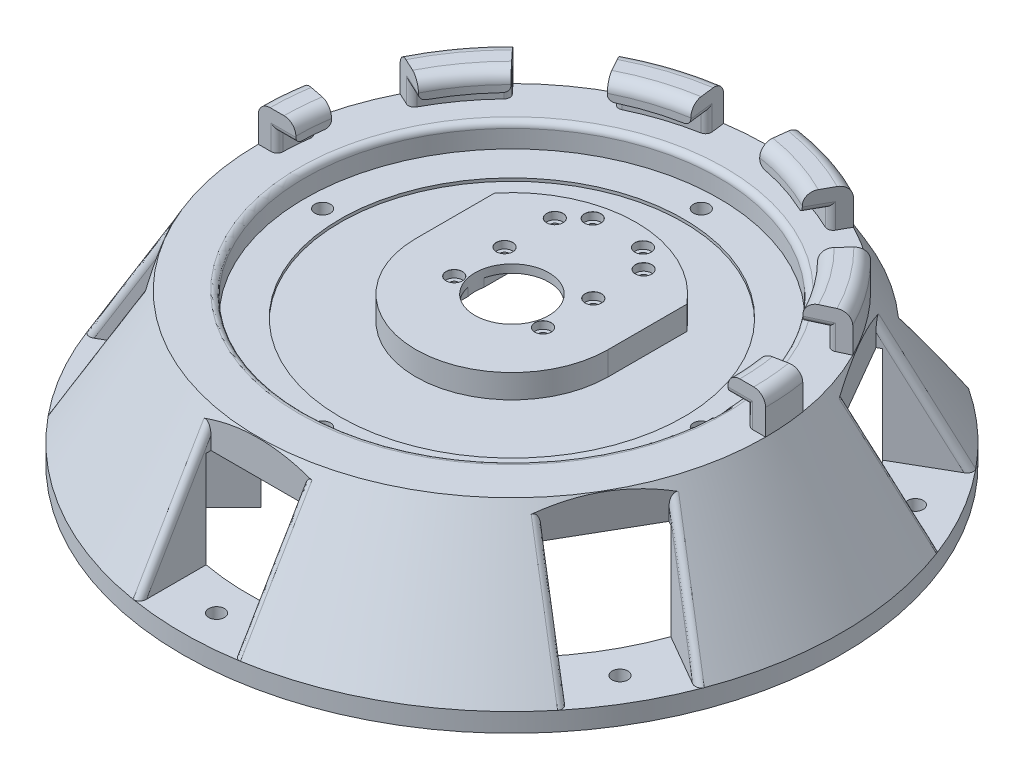
SolidWorks part; units mm, degrees
note: The reader was unsure of these and kept them because the rebuilt part matched: shared geometry of "Sketch3<3>".
material "PLA"
ref_plane "Front Plane" through (0, 0, 0) normal (0, 0, 1) x (1, 0, 0)
ref_plane "Top Plane" through (0, 0, 0) normal (0, 1, 0) x (1, 0, 0)
ref_plane "Right Plane" through (0, 0, 0) normal (1, 0, 0) x (0, 0, -1)
sketch "Sketch1" plane through (0, 0, 0) normal (0, 0, 1) x (1, 0, 0)
  line L0 (0, 0) -> (-85.725, 0)
  line L1 (-85.725, 0) -> (-115.0544, -50.8)
  line L2 (-115.0544, -50.8) -> (0, -50.8)
  line L6 (0, 0) -> (0, -50.8) construction
  line L7 (0, 0) -> (0, -50.8)
  dimension "D1" = 85.725
  dimension "D2" = 115.0544
  dimension "D3" = 50.8
revolve "Revolve1" add sketch "Sketch1" angle 360 about L6
sketch "Sketch2" plane through (0, 0, 0) normal (0, 1, 0) x (1, 0, 0)
  circle A0 centre (0, 0) radius 12.5
  dimension "D1" = 25
extrude "Cut-Extrude1" cut sketch "Sketch2" against normal through all
sketch "Sketch3" plane through (0, 0, 0) normal (0, 1, 0) x (1, 0, 0)
  line L0 (-32.5, 0) -> (-32.5, 26.6036)
  line L1 (-32.5, 26.6036) -> (32.5, 26.6036)
  line L2 (32.5, 26.6036) -> (32.5, 0)
  circle A0 centre (0, 0) radius 32.5
  circle A1 centre (0, 0) radius 70
  circle A2 centre (0, 0) radius 42
  circle M1 centre (0, 0) radius 12.5
  dimension "D1" = 65
  dimension "D2" = 140
  dimension "D3" = 84
extrude "Cut-Extrude2" cut sketch "Sketch3" against normal blind 8 contours A1 A0 L0 L1 L2 | A1 A2
sketch "Sketch7" plane through (0, -50.8, 0) normal (0, -1, 0) x (1, 0, 0)
  line L0 (0, 88.9) -> (0, -161.1) construction
  line L1 (-85.4, 0) -> (85.4, 0) construction
  line L2 (-60, -65.5989) -> (-60, -161.1)
  line L3 (-60, -161.1) -> (60, -161.1)
  line L4 (60, -161.1) -> (60, -65.5989)
  line L5 (-60, -65.5989) -> (60, -65.5989) construction
  arc A2 (60, -65.5989) -> (-60, -65.5989) centre (0, 0) ccw
  dimension "D1" = 177.8
  dimension "D2" = 25.4
  dimension "D3" = 25.4
  dimension "D4" = 120
  dimension "D5" = 250
extrude "Cut-Extrude5" cut sketch "Sketch7" against normal blind 39 contours L3 L4 A2 L2
sketch "Sketch8" plane through (0, 0, 0) normal (0, 1, 0) x (1, 0, 0)
  line L0 (0, 0) -> (0, -115.0544) construction
  line L2 (-15.875, -123.925) -> (15.875, -123.925)
  line L3 (-15.875, -123.925) -> (-15.875, -85.825)
  line L4 (-15.875, -85.825) -> (15.875, -85.825)
  line L5 (15.875, -123.925) -> (15.875, -85.825)
  line L6 (-15.875, -123.925) -> (15.875, -85.825) construction
  line L7 (-15.875, -85.825) -> (15.875, -123.925) construction
  arc A0 (-60, 98.1708) -> (60, 98.1708) centre (0, 0) ccw construction
  point P6 (0, -104.875)
  dimension "D1" = 85.825
  dimension "D2" = 38.1
  dimension "D3" = 31.75
extrude "Cut-Extrude6" cut sketch "Sketch8" against normal blind 44.45
pattern_circular "CirPattern2" count 6 over 360 about axis through (0, 0, 0) along (0, 1, 0) of "Cut-Extrude6"
sketch "Sketch9" plane through (0, 0, 0) normal (0, 1, 0) x (1, 0, 0)
  line L0 (0, 0) -> (0, -115.0544) construction
  arc A0 (-60, 98.1708) -> (60, 98.1708) centre (0, 0) ccw construction
  circle A1 centre (0, -99.8144) radius 2.65
  dimension "D1" = 5.3
  dimension "D2" = 15.24
extrude "Cut-Extrude7" cut sketch "Sketch9" against normal through all
pattern_circular "CirPattern3" count 6 over 360 about axis through (0, 0, 0) along (0, 1, 0) of "Cut-Extrude7"
sketch "Sketch12" plane through (0, 0, 0) normal (0, 0, 1) x (1, 0, 0)
  line L0 (85.725, 0) -> (85.725, 12.7)
  line L1 (85.725, 12.7) -> (73.025, 12.7)
  line L2 (73.025, 12.7) -> (73.025, 6.35)
  line L3 (73.025, 6.35) -> (79.375, 6.35)
  line L4 (79.375, 6.35) -> (79.375, 0)
  line L5 (85.725, 0) -> (-85.725, 0) construction
  line L6 (0, 0) -> (0, 12.7) construction
  line L7 (12.5, 0) -> (-12.5, 0) construction
  line L8 (79.375, 0) -> (85.725, 0)
  point P13 (0, 6.35)
  dimension "D1" = 6.35
  dimension "D2" = 73.025
  dimension "D3" = 79.375
  dimension "D4" = 12.7
  dimension "D5" = 12.7
revolve "Revolve2" add sketch "Sketch12" angle 180 about L6
sketch "Sketch15" plane through (0, -11.8, 0) normal (0, -1, 0) x (1, 0, 0)
  line L0 (0, -1000) -> (0, 49000) construction
  point P1 (-15, 4.5)
  point P4 (-15, -12.5)
  point P5 (-15, -29.5)
  point P6 (-8.5, -35.8)
  point P7 (8.5, -35.8)
  point P8 (15, -29.5)
  point P9 (15, -12.5)
  point P10 (15, 4.5)
  dimension "D1" = 17
  dimension "D2" = 17
  dimension "D3" = 4.5
  dimension "D4" = 15
  dimension "D5" = 8.5
  dimension "D6" = 35.8
sketch "Sketch18" plane through (0, 12.7, 0) normal (0, 1, 0) x (1, 0, 0)
  line L0 (46.6433, 89.7185) -> (70.9138, 72.0849)
  line L1 (0, 201000) -> (0, -249000) construction
  line L2 (-15, 100) -> (-9, 50)
  line L3 (-9, 50) -> (9, 50)
  line L4 (9, 50) -> (15, 100)
  line L5 (-15, 100) -> (15, 100)
  line L6 (36.6704, 35.1608) -> (70.9138, 72.0849)
  line L7 (22.1081, 45.7409) -> (36.6704, 35.1608)
  line L8 (46.6433, 89.7185) -> (22.1081, 45.7409)
  line L9 (90.4704, 45.1675) -> (99.7409, 16.6359)
  line L10 (50.334, 6.8913) -> (99.7409, 16.6359)
  line L11 (44.7717, 24.0104) -> (50.334, 6.8913)
  line L12 (90.4704, 45.1675) -> (44.7717, 24.0104)
  line L13 (99.7409, -16.6359) -> (90.4704, -45.1675)
  line L14 (44.7717, -24.0104) -> (90.4704, -45.1675)
  line L15 (50.334, -6.8913) -> (44.7717, -24.0104)
  line L16 (99.7409, -16.6359) -> (50.334, -6.8913)
  line L17 (70.9138, -72.0849) -> (46.6433, -89.7185)
  line L18 (22.1081, -45.7409) -> (46.6433, -89.7185)
  line L19 (36.6704, -35.1608) -> (22.1081, -45.7409)
  line L20 (70.9138, -72.0849) -> (36.6704, -35.1608)
  line L21 (15, -100) -> (-15, -100)
  line L22 (-9, -50) -> (-15, -100)
  line L23 (9, -50) -> (-9, -50)
  line L24 (15, -100) -> (9, -50)
  line L25 (-46.6433, -89.7185) -> (-70.9138, -72.0849)
  line L26 (-36.6704, -35.1608) -> (-70.9138, -72.0849)
  line L27 (-22.1081, -45.7409) -> (-36.6704, -35.1608)
  line L28 (-46.6433, -89.7185) -> (-22.1081, -45.7409)
  line L29 (-90.4704, -45.1675) -> (-99.7409, -16.6359)
  line L30 (-50.334, -6.8913) -> (-99.7409, -16.6359)
  line L31 (-44.7717, -24.0104) -> (-50.334, -6.8913)
  line L32 (-90.4704, -45.1675) -> (-44.7717, -24.0104)
  line L33 (-99.7409, 16.6359) -> (-90.4704, 45.1675)
  line L34 (-44.7717, 24.0104) -> (-90.4704, 45.1675)
  line L35 (-50.334, 6.8913) -> (-44.7717, 24.0104)
  line L36 (-99.7409, 16.6359) -> (-50.334, 6.8913)
  line L37 (-70.9138, 72.0849) -> (-46.6433, 89.7185)
  line L38 (-22.1081, 45.7409) -> (-46.6433, 89.7185)
  line L39 (-36.6704, 35.1608) -> (-22.1081, 45.7409)
  line L40 (-70.9138, 72.0849) -> (-36.6704, 35.1608)
  point P4 (0, 50)
  point P7 (0, 100)
  point P48 (0, 0)
  dimension "D1" = 18
  dimension "D2" = 50
  dimension "D3" = 30
  dimension "D4" = 50
  dimension "D5" = 10
extrude "Cut-Extrude9" cut sketch "Sketch18" against normal blind 12.7
sketch "Sketch20" plane through (0, -11.8, 0) normal (0, -1, 0) x (1, 0, 0)
  line L0 (-22.5, -33) -> (-12.5, -40)
  line L1 (22.5, 23) -> (-22.5, 23)
  line L2 (22.5, 23) -> (22.5, -40)
  line L3 (22.5, -40) -> (-22.5, -40)
  line L4 (-22.5, 23) -> (-22.5, -40)
  line L7 (-12.5, -40) -> (12.5, -40)
  line L8 (12.5, -40) -> (22.5, -33)
  point P0 (0, -10)
  dimension "D1" = 23
  dimension "D2" = 45
  dimension "D3" = 10
  dimension "D4" = 10
  dimension "D5" = 7
  dimension "D6" = 7
  dimension "D7" = 10
  dimension "D8" = 40
  dimension "D9" = 22.5
extrude "Cut-Extrude11" cut sketch "Sketch3<3>" against normal blind 1 contours A0 L1 M1 | A0 L1 L0 | L1 A0 | L1 A2 A0 | A0 L2 L1
sketch "Sketch3<3>" plane through (0, 0, 0) normal (0, 1, 0) x (1, 0, 0) same geometry as "Sketch3"
sketch "Sketch22" plane through (0, -1, 0) normal (0, 1, 0) x (1, 0, 0)
  circle A0 centre (-15, 12.5) radius 1.4
  circle A1 centre (-15, 29.5) radius 1.4
  circle A2 centre (-8.5, 35.8) radius 1.4
  circle A3 centre (8.5, 35.8) radius 1.4
  circle A4 centre (15, 29.5) radius 1.4
  circle A5 centre (15, 12.5) radius 1.4
  circle A6 centre (15, -4.5) radius 1.4
  circle A7 centre (-15, -4.5) radius 1.4
  dimension "D1" = 17
  dimension "D2" = 17
  dimension "D3" = 2.8
  dimension "D4" = 2.8
  dimension "D5" = 2.8
  dimension "D6" = 2.8
  dimension "D7" = 2.8
  dimension "D8" = 2.8
  dimension "D9" = 2.8
  dimension "D10" = 2.8
  dimension "D11" = 17
  dimension "D12" = 30
  dimension "D13" = 30
  dimension "D14" = 30
  dimension "D15" = 17
  dimension "D16" = 17
  dimension "D17" = 6.3
  dimension "D18" = 6.3
  dimension "D19" = 35.8
  dimension "D20" = 8.5
  dimension "D21" = 35.8
  dimension "D22" = 15
  dimension "D23" = 19.5256
  dimension "D24" = 15.6605
hole_wizard "CBORE for M2.5 SHCS1" positions "Sketch23" profile "Sketch24" counterbore size "M2.5" standard "ANSI Metric" end condition through all
sketch "Sketch23" plane through (0, -1, 0) normal (0, 1, 0) x (1, 0, 0)
  point P0 (-15, -4.5)
  point P3 (-15, 12.5)
  point P6 (-15, 29.5)
  point P9 (-8.5, 35.8)
  point P12 (8.5, 35.8)
  point P15 (15, 29.5)
  point P18 (15, 12.5)
  point P21 (15, -4.5)
sketch "Sketch24" plane through (-15, -1, 4.5) normal (1, 0, 0) x (0, 0, 1)
  line L0 (0, 0) -> (0, 49.8)
  line L1 (0, 49.8) -> (1.45, 49.8)
  line L3 (1.45, 49.8) -> (1.45, 2.5)
  line L4 (2.75, 2.5) -> (1.45, 2.5)
  line L5 (2.75, 2.5) -> (2.75, 0.025)
  line L6 (2.75, 0.025) -> (2.775, 0)
  line L7 (2.775, 0) -> (0, 0)
  line L8 (-2.75, 0.025) -> (-2.775, 0) construction
  line L11 (0, -6.35) -> (0, 107.95) construction
  dimension "Thru Hole Dia." = 2.9
  dimension "Thru Hole Depth" = 49.8
  dimension "C'Bore Dia." = 5.5
  dimension "C'Bore Depth" = 2.5
  dimension "Near C'Sink Dia." = 5.55
  dimension "Near C'Sink Angle" = 90
fillet "Fillet1" radius 4 12 edges at (85.4509, 12.7, -6.8497) (69.353, 12.7, -50.3879) (26.4905, 12.7, -81.5293) (-26.4905, 12.7, -81.5293) (-69.353, 12.7, -50.3879) (-85.4509, 12.7, -6.8497) (-72.8088, 12.7, -5.6148) (-59.0785, 12.7, -42.923) (-22.566, 12.7, -69.4509) (22.566, 12.7, -69.4509) (59.0785, 12.7, -42.923) (72.8088, 12.7, -5.6148)
fillet "Fillet2" radius 2 12 edges at (75.2789, 6.35, -11.8112) (76.2, 6.35, 0) (53.9595, 6.35, -53.8033) (67.8444, 6.35, -34.6924) (12.0293, 6.35, -75.2444) (34.4956, 6.35, -67.9447) (-12.0293, 6.35, -75.2444) (-34.4956, 6.35, -67.9447) (-53.9595, 6.35, -53.8033) (-67.8444, 6.35, -34.6924) (-75.2789, 6.35, -11.8112) (-76.2, 6.35, 0)
fillet "Fillet3" radius 2 12 edges at (-78.3963, 4.175, -12.4261) (-56.1201, 4.175, -56.1331) (-70.7278, 4.175, -36.0273) (-12.4079, 4.175, -78.3992) (56.1201, 4.175, -56.1331) (78.3963, 4.175, -12.4261) (-79.375, 4.175, 0) (-36.0437, 4.175, -70.7195) (12.4079, 4.175, -78.3992) (36.0437, 4.175, -70.7195) (70.7278, 4.175, -36.0273) (79.375, 4.175, 0)
fillet "Fillet4" radius 2 10 edges
fillet "Fillet5" radius 2 1 edges at (0, 0, 70)
fillet "Fillet9" radius 1 2 edges
sketch "Sketch28" plane through (0, -11.8, 0) normal (0, -1, 0) x (1, 0, 0)
  line L0 (9.2, 12) -> (-9.2, 12)
  line L1 (-12.2, 9) -> (-12.2, -30)
  line L2 (-9.2, -33) -> (9.2, -33)
  line L3 (12.2, -30) -> (12.2, 9)
  arc A0 (-9.2, 12) -> (-12.2, 9) centre (-9.2, 9) ccw
  arc A1 (-12.2, -30) -> (-9.2, -33) centre (-9.2, -30) ccw
  arc A2 (9.2, -33) -> (12.2, -30) centre (9.2, -30) ccw
  arc A3 (12.2, 9) -> (9.2, 12) centre (9.2, 9) ccw
extrude "Cut-Extrude12" cut sketch "Sketch28" against normal offset from surface (8.05 mm away) 2.75
extrude "Cut-Extrude15" cut sketch "Sketch20" against normal offset from surface (5.3 mm away) 2.75
sketch "Sketch29" plane through (0, -8, 0) normal (0, 1, 0) x (1, 0, 0)
  point P0 (0, 64)
  point P5 (64, 0)
  point P6 (0, -64)
  point P7 (-64, 0)
  point P8 (0, 0)
  dimension "D1" = 64
  dimension "D2" = 4
hole_wizard "M5 Clearance Hole1" positions "Sketch32" profile "Sketch33" hole size "M5" standard "ANSI Metric" end condition up to next
sketch "Sketch32" plane through (0, -8, 0) normal (0, 1, 0) x (1, 0, 0)
  point P0 (0, 64)
  point P3 (64, 0)
  point P6 (0, -64)
  point P9 (-64, 0)
sketch "Sketch33" plane through (0, -8, -64) normal (1, 0, 0) x (0, 0, 1)
  line L0 (0, 0) -> (0, 3.8)
  line L1 (0, 3.8) -> (2.65, 3.8)
  line L2 (2.65, 3.8) -> (2.65, 0)
  line L5 (2.65, 0) -> (0, 0)
  line L11 (0, -6.35) -> (0, 107.95) construction
  dimension "Thru Hole Dia." = 5.3
  dimension "Thru Hole Depth" = 3.8
sketch "Sketch34" plane through (0, -8, 0) normal (0, 1, 0) x (1, 0, 0)
  circle A0 centre (0, 0) radius 70
  circle A1 centre (0, 0) radius 58
  line M5 (-32.5, 0) -> (-32.5, 26.6036)
  arc M6 (-32.5, 26.6036) -> (32.5, 26.6036) centre (0, 0) cw
  line M7 (32.5, 26.6036) -> (32.5, 0)
  arc M8 (32.5, 0) -> (-32.5, 0) centre (0, 0) cw
  dimension "D1" = 140
  dimension "D2" = 116
extrude "Cut-Extrude16" cut sketch "Sketch34" against normal blind 1 contours A1 M8 M5 M6 M7
sketch "Sketch37" plane through (0, 0, 0) normal (0, 1, 0) x (1, 0, 0)
  circle A0 centre (0, 0) radius 111.3882
  dimension "D1" = 222.7764
sketch "Sketch39" plane through (0, -50.8, 0) normal (0, -1, 0) x (1, 0, 0)
  line L0 (-67.1751, 67.1751) -> (-42.4264, 42.4264)
  line L1 (-72, 12.5) -> (-107, 12.5)
  line L2 (-72, 12.5) -> (-72, -12.5)
  line L3 (-72, -12.5) -> (-107, -12.5)
  line L4 (-107, 12.5) -> (-107, -12.5)
  line L5 (-72, 0) -> (0, 0) construction
  line L6 (0, 0) -> (72, 0) construction
  line L7 (107, 12.5) -> (72, 12.5)
  line L8 (107, 12.5) -> (107, -12.5)
  line L9 (107, -12.5) -> (72, -12.5)
  line L10 (72, 12.5) -> (72, -12.5)
  line L13 (-42.4264, 42.4264) -> (-29.6985, 55.1543)
  line L14 (-29.6985, 55.1543) -> (-54.4472, 79.9031)
  line L15 (-54.4472, 79.9031) -> (-67.1751, 67.1751)
  line L16 (54.4472, 79.9031) -> (29.6985, 55.1543)
  line L17 (29.6985, 55.1543) -> (42.4264, 42.4264)
  line L18 (42.4264, 42.4264) -> (67.1751, 67.1751)
  line L19 (67.1751, 67.1751) -> (54.4472, 79.9031)
  line L21 (0, 0) -> (101.0152, 101.0152) construction
  line L22 (0, 0) -> (-104.6054, 104.6054) construction
  arc M26 (-60, -65.5989) -> (60, -65.5989) centre (0, 0) cw
  dimension "D1" = 25
  dimension "D2" = 35
  dimension "D3" = 35
  dimension "D4" = 35
  dimension "D5" = 72
  dimension "D6" = 72
  dimension "D7" = 60
  dimension "D8" = 60
  dimension "D9" = 18
  dimension "D10" = 18
  dimension "D11" = 35
  dimension "D12" = 25
extrude "Boss-Extrude1" add sketch "Sketch39" along a picked direction on the side against the normal up to next (39 mm away) contours L13 L14 L0 M26 | L3 L2 L1 M26 | L17 L18 L16 M26 | L7 L10 L9 M26
fillet "Fillet10" radius 10 2 edges at (36.0624, -11.8, 48.7904) (-36.0624, -11.8, 48.7904)
extrude "Cut-Extrude-Thin1" cut sketch "Sketch37" against normal through all thin
